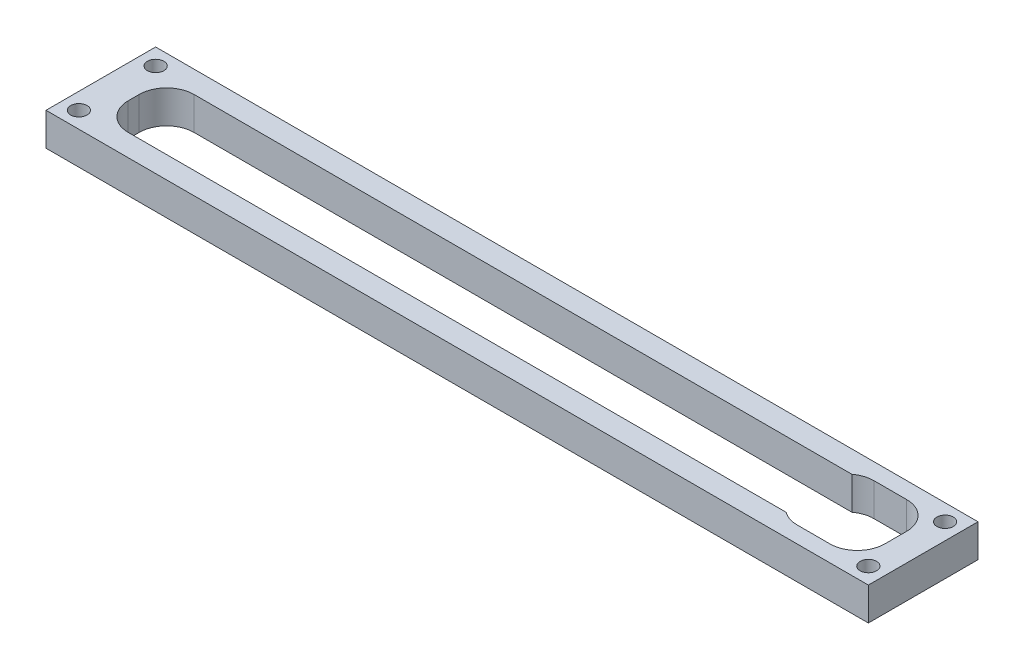
SolidWorks part; units mm, degrees
ref_plane "Front Plane" through (0, 0, 0) normal (0, 0, 1) x (1, 0, 0)
ref_plane "Top Plane" through (0, 0, 0) normal (0, 1, 0) x (1, 0, 0)
ref_plane "Right Plane" through (0, 0, 0) normal (1, 0, 0) x (0, 0, -1)
sketch "Sketch1" plane through (0, 0, 0) normal (0, 1, 0) x (1, 0, 0)
  line L0 (75, 20) -> (75, 0) construction
  line L1 (0, 0) -> (150, 0)
  line L2 (0, 0) -> (0, 20)
  line L3 (0, 20) -> (150, 20)
  line L4 (150, 0) -> (150, 20)
  line L5 (0, 10) -> (150, 10) construction
  line L6 (75, 16) -> (75, 4) construction
  line L7 (6, 16) -> (144, 16)
  line L8 (6, 16) -> (6, 4)
  line L9 (6, 4) -> (144, 4)
  line L10 (144, 16) -> (144, 4)
  line L11 (6, 10) -> (144, 10) construction
  circle A0 centre (3, 17) radius 1.5
  circle A1 centre (3, 3) radius 1.5
  circle A2 centre (147, 3) radius 1.5
  circle A3 centre (147, 17) radius 1.5
  point P17 (75, 10)
  point P18 (75, 10)
  dimension "D7" = 3
  dimension "D1" = 150
  dimension "D2" = 20
  dimension "D3" = 138
  dimension "D4" = 12
  dimension "D5" = 3
  dimension "D6" = 3
extrude "Boss-Extrude1" add sketch "Sketch1" along normal blind 6
sketch "Sketch2" plane through (0, 6, 0) normal (0, 1, 0) x (1, 0, 0)
  line L0 (92, 10) -> (-49908, 10) construction
  line L1 (144, 4) -> (144, 16) construction
  line L2 (131, 17) -> (131, 16)
  line L5 (144, 16) -> (6, 16) construction
  line L6 (138, 17) -> (138, 3) construction
  line L7 (131, 17) -> (145, 17)
  line L9 (131, 3) -> (145, 3)
  line L10 (145, 17) -> (145, 3)
  line L12 (131, 16) -> (144, 16)
  line L13 (144, 16) -> (144, 4)
  line L14 (144, 4) -> (131, 4)
  line L15 (6, 4) -> (144, 4) construction
  line L16 (131, 4) -> (131, 3)
  circle A2 centre (147, 17) radius 1.5 construction
  point P4 (144, 10)
  point P23 (138, 10)
  dimension "D1" = 1
  dimension "D2" = 14
  dimension "D3" = 14
extrude "Cut-Extrude1" cut sketch "Sketch2" against normal through all
fillet "Fillet1" radius 5 6 edges at (145, 3, -17) (145, 3, -3) (131, 3, -17) (131, 3, -3) (6, 3, -4) (6, 3, -16)
equation "\"TrackLength\"= 150"
equation "\"D1@Sketch1\"=\"TrackLength\""
equation "\"TrackWidth\" = \"MarbleTrackWidth\" + ( 2 * 4 )"
equation "\"D2@Sketch1\"=\"TrackWidth\""
equation "\"MarbleTrackWidth\"= \"MarbleWidth\" - 1"
equation "\"MarbleTrackLength\"= \"TrackLength\" - ( 2 * 6 )"
equation "\"D3@Sketch1\"=\"MarbleTrackLength\""
equation "\"D4@Sketch1\"=\"MarbleTrackWidth\""
equation "\"MarbleWidth\"= 13"
